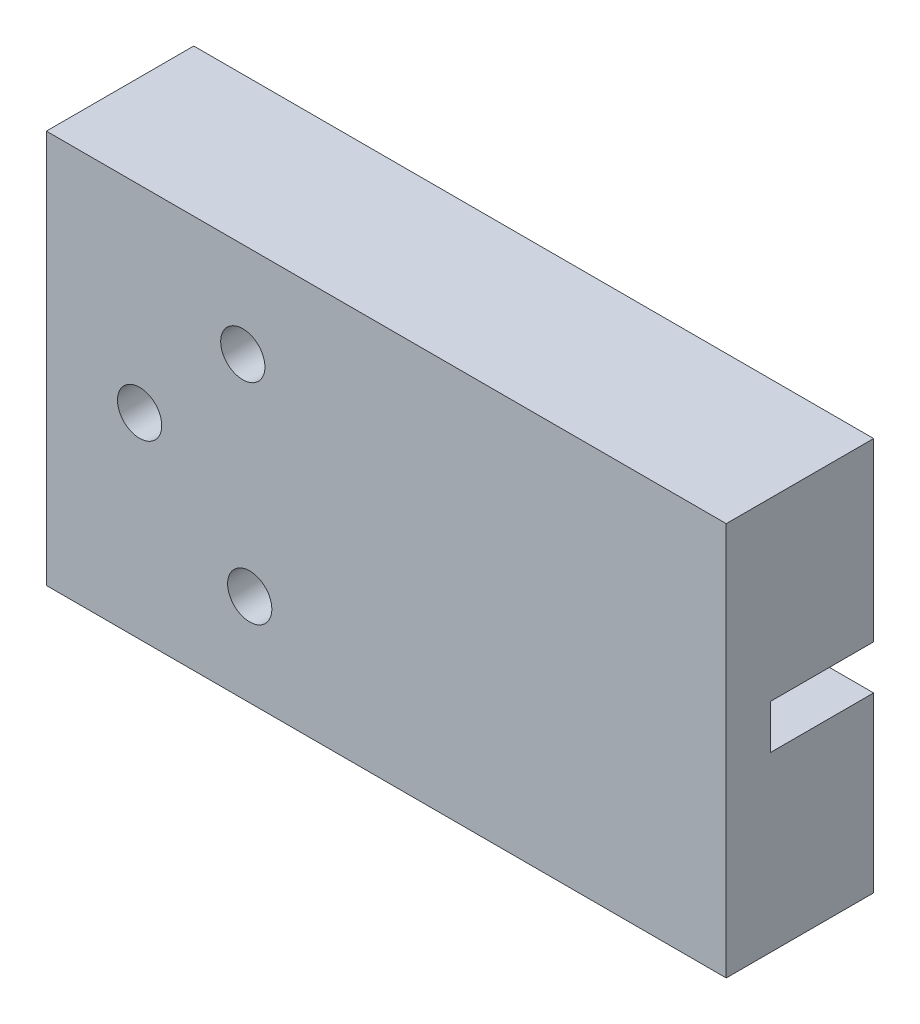
SolidWorks part; units mm, degrees
ref_plane "Plan de face" through (0, 0, 0) normal (0, 0, 1) x (1, 0, 0)
ref_plane "Plan de dessus" through (0, 0, 0) normal (0, 1, 0) x (1, 0, 0)
ref_plane "Plan de droite" through (0, 0, 0) normal (1, 0, 0) x (0, 0, -1)
sketch "Esquisse1" plane through (0, 0, 0) normal (0, 0, 1) x (1, 0, 0)
  circle A0 centre (-18.394, 17.8631) radius 50
  dimension "D1" = 100
extrude "Boss.-Extru.1" add sketch "Esquisse1" along normal blind 10
sketch "Esquisse2" plane through (0, 0, 0) normal (0, 0, -1) x (-1, 0, 0)
  circle A0 centre (18.394, 17.8631) radius 10
  circle A4 centre (18.394, 17.8631) radius 50 construction
  dimension "D1" = 20
  dimension "D2" = 40
extrude "Enlèv. mat.-Extru.1" cut sketch "Esquisse2" against normal blind 7
sketch "Esquisse4" plane through (0, 0, 0) normal (0, 0, -1) x (-1, 0, 0)
  line L1 (13.6656, 19.3631) -> (-38.5885, 19.3631)
  line L2 (13.6656, 19.3631) -> (13.6656, 16.3631)
  line L3 (13.6656, 16.3631) -> (-38.5885, 16.3631)
  line L4 (-38.5885, 19.3631) -> (-38.5885, 16.3631)
  circle A1 centre (18.394, 17.8631) radius 50 construction
  dimension "D1" = 3
  dimension "D2" = 1.5
extrude "Enlèv. mat.-Extru.2" cut sketch "Esquisse4" against normal blind 7
sketch "Esquisse6" plane through (0, 0, 0) normal (0, 0, -1) x (-1, 0, 0)
  line L1 (-31.8143, 71.3621) -> (77.2564, 71.3621)
  line L2 (-31.8143, 71.3621) -> (-31.8143, 31.3086)
  line L3 (-31.8143, 31.3086) -> (77.2564, 31.3086)
  line L4 (77.2564, 71.3621) -> (77.2564, 31.3086)
extrude "Enlèv. mat.-Extru.3" cut sketch "Esquisse6" against normal blind 10
sketch "Esquisse8" plane through (0, 0, 0) normal (0, 0, -1) x (-1, 0, 0)
  line L1 (75.3431, -32.0235) -> (31.8877, -32.0235)
  line L2 (75.3431, -32.0235) -> (75.3431, 40.996)
  line L3 (75.3431, 40.996) -> (31.8877, 40.996)
  line L4 (31.8877, -32.0235) -> (31.8877, 40.996)
extrude "Enlèv. mat.-Extru.4" cut sketch "Esquisse8" against normal blind 10
sketch "Esquisse9" plane through (0, 0, 0) normal (0, 0, -1) x (-1, 0, 0)
  line L1 (41.6051, -36.7211) -> (-41.6048, -36.7211)
  line L2 (41.6051, -36.7211) -> (41.6051, 4.6153)
  line L3 (41.6051, 4.6153) -> (-41.6048, 4.6153)
  line L4 (-41.6048, -36.7211) -> (-41.6048, 4.6153)
extrude "Enlèv. mat.-Extru.5" cut sketch "Esquisse9" against normal blind 10
sketch "Esquisse10" plane through (0, 0, 0) normal (0, 0, -1) x (-1, 0, 0)
  line L1 (-14.2326, 40.0528) -> (-46.2301, 40.0528)
  line L2 (-14.2326, 40.0528) -> (-14.2326, -10.5706)
  line L3 (-14.2326, -10.5706) -> (-46.2301, -10.5706)
  line L4 (-46.2301, 40.0528) -> (-46.2301, -10.5706)
  line L6 (-14.2326, 12.9026) -> (-14.2326, 12.3073)
  line L8 (-10.3832, 12.9026) -> (-10.3832, 12.3073)
extrude "Enlèv. mat.-Extru.6" cut sketch "Esquisse10" against normal blind 10 contours L2 L3 L4 L1
sketch "Esquisse11" plane through (0, 0, 7) normal (0, 0, -1) x (-1, 0, 0)
  circle A0 centre (18.5621, 24.8631) radius 1.5
  arc A3 (8.5071, 16.3631) -> (8.5071, 19.3631) centre (18.394, 17.8631) ccw construction
  dimension "D1" = 7
extrude "Enlèv. mat.-Extru.7" cut sketch "Esquisse11" against normal blind 10
sketch "Esquisse12" plane through (0, 0, 7) normal (0, 0, -1) x (-1, 0, 0)
  circle A0 centre (18.0917, 10.8696) radius 1.5
  arc A1 (8.5071, 16.3631) -> (8.5071, 19.3631) centre (18.394, 17.8631) ccw construction
  dimension "D1" = 7
extrude "Enlèv. mat.-Extru.8" cut sketch "Esquisse12" against normal blind 10
sketch "Esquisse13" plane through (0, 0, 7) normal (0, 0, -1) x (-1, 0, 0)
  circle A0 centre (25.5621, 17.9221) radius 1.5
  circle A1 centre (18.5621, 24.8631) radius 1.5 construction
  dimension "D1" = 7
  dimension "D2" = 3
extrude "Enlèv. mat.-Extru.9" cut sketch "Esquisse13" against normal blind 10
sketch "Esquisse14" plane through (0, 0, 7) normal (0, 0, -1) x (-1, 0, 0)
  circle A0 centre (11.6228, 17.977) radius 1.5
